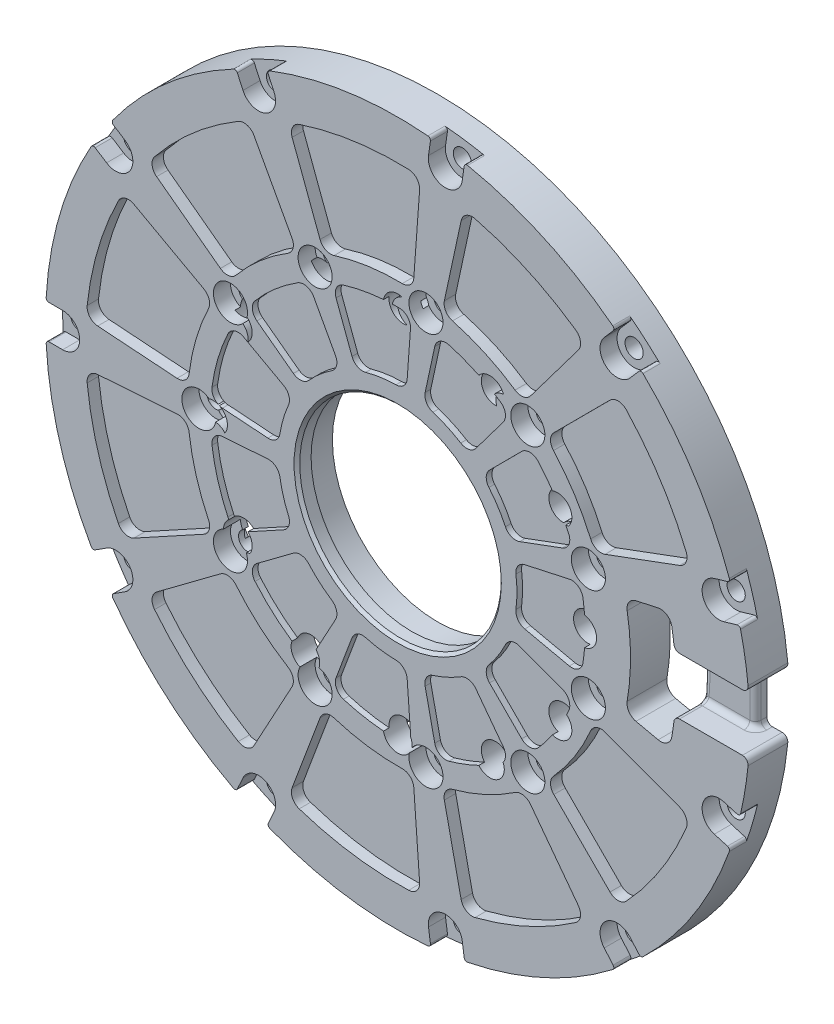
SolidWorks part; units mm, degrees
material "ABS"
ref_plane "Front Plane" through (0, 0, 0) normal (0, 0, 1) x (1, 0, 0)
ref_plane "Top Plane" through (0, 0, 0) normal (0, 1, 0) x (1, 0, 0)
ref_plane "Right Plane" through (0, 0, 0) normal (1, 0, 0) x (0, 0, -1)
ref_plane "Plane1" through (0, 0, 15) normal (0, 0, 1) x (1, 0, 0)
sketch "Sketch1" plane through (0, 0, 15) normal (0, 0, 1) x (1, 0, 0)
  circle A0 centre (0, 0) radius 39.1
  circle A1 centre (0, 0) radius 32.5 construction
  circle A2 centre (32.5, 0) radius 2.525
  circle A3 centre (28.1458, -16.25) radius 2.525
  circle A4 centre (16.25, -28.1458) radius 2.525
  circle A5 centre (0, -32.5) radius 2.525
  circle A6 centre (-16.25, -28.1458) radius 2.525
  circle A7 centre (-28.1458, -16.25) radius 2.525
  circle A8 centre (-32.5, 0) radius 2.525
  circle A9 centre (-28.1458, 16.25) radius 2.525
  circle A10 centre (-16.25, 28.1458) radius 2.525
  circle A11 centre (0, 32.5) radius 2.525
  circle A12 centre (16.25, 28.1458) radius 2.525
  circle A13 centre (0, 0) radius 16
  circle A14 centre (28.1458, 16.25) radius 2.525
  point P28 (0, 0)
extrude "Boss-Extrude1" add sketch "Sketch1" along normal blind 7
sketch "Sketch2" plane through (0, 0, 15) normal (0, 0, -1) x (-1, 0, 0)
  circle A0 centre (0, 0) radius 18.5
  dimension "D1" = 37
extrude "Cut-Extrude1" cut sketch "Sketch2" against normal blind 4.5
sketch "Sketch3" plane through (0, 0, 22) normal (0, 0, 1) x (1, 0, 0)
  circle A1 centre (-16.25, 28.1458) radius 2.55
  circle A2 centre (1.5464, 32.4632) radius 2.55
  circle A4 centre (18.8518, 26.4737) radius 2.55
  circle A6 centre (30.172, 12.079) radius 2.55
  circle A8 centre (31.9127, -6.1507) radius 2.55
  circle A10 centre (23.5214, -22.4276) radius 2.55
  circle A12 centre (7.6622, -31.5839) radius 2.55
  circle A14 centre (-10.6297, -30.7125) radius 2.55
  circle A16 centre (-25.5467, -20.0902) radius 2.55
  circle A18 centre (-32.3528, -3.0893) radius 2.55
  circle A20 centre (-28.8872, 14.8924) radius 2.55
  point P36 (0, 0)
  dimension "D1" = 5.1
  dimension "D3" = 11
extrude "Boss-Extrude2" add sketch "Sketch3" against normal blind 2
chamfer "Chamfer3" distance 0.5 angle 45 11 edges at (35.025, 0, 15) (30.6708, -16.25, 15) (18.775, -28.1458, 15) (2.525, -32.5, 15) (-13.725, -28.1458, 15) (-25.6208, -16.25, 15) (-29.975, 0, 15) (-25.6208, 16.25, 15) (-13.725, 28.1458, 15) (2.525, 32.5, 15) (18.775, 28.1458, 15)
sketch "Sketch4" plane through (0, 0, 15) normal (0, 0, -1) x (-1, 0, 0)
  arc A0 (6.4473, 32.3131) -> (-6.4473, 32.3131) centre (0, 32.5) ccw
  circle A1 centre (0, 0) radius 39.1
  arc A2 (22.8936, 23.6978) -> (12.046, 30.6692) centre (17.5708, 27.3407) ccw
  arc A3 (32.0713, 7.5587) -> (26.7147, 19.288) centre (29.563, 13.501) ccw
  arc A4 (31.0666, -10.9803) -> (32.9017, 1.783) centre (32.1692, -4.6252) ccw
  arc A5 (20.1985, -26.0331) -> (28.6427, -16.288) centre (24.5619, -21.283) ccw
  arc A6 (2.9175, -32.8206) -> (15.2898, -29.1878) centre (9.1563, -31.1835) ccw
  arc A7 (-15.2898, -29.1878) -> (-2.9175, -32.8206) centre (-9.1563, -31.1835) ccw
  arc A8 (-28.6427, -16.288) -> (-20.1985, -26.0331) centre (-24.5619, -21.283) ccw
  arc A9 (-32.9017, 1.783) -> (-31.0666, -10.9803) centre (-32.1692, -4.6252) ccw
  arc A10 (-26.7147, 19.288) -> (-32.0713, 7.5587) centre (-29.563, 13.501) ccw
  arc A11 (-12.046, 30.6692) -> (-22.8936, 23.6978) centre (-17.5708, 27.3407) ccw
  arc A12 (-32.0713, 7.5587) -> (-32.9017, 1.783) centre (0, 0) ccw
  arc A13 (-22.8936, 23.6978) -> (-26.7147, 19.288) centre (0, 0) ccw
  arc A14 (-6.4473, 32.3131) -> (-12.046, 30.6692) centre (0, 0) ccw
  arc A15 (12.046, 30.6692) -> (6.4473, 32.3131) centre (0, 0) ccw
  arc A16 (26.7147, 19.288) -> (22.8936, 23.6978) centre (0, 0) ccw
  arc A17 (32.9017, 1.783) -> (32.0713, 7.5587) centre (0, 0) ccw
  arc A18 (28.6427, -16.288) -> (31.0666, -10.9803) centre (0, 0) ccw
  arc A19 (15.2898, -29.1878) -> (20.1985, -26.0331) centre (0, 0) ccw
  arc A20 (-2.9175, -32.8206) -> (2.9175, -32.8206) centre (0, 0) ccw
  arc A21 (-20.1985, -26.0331) -> (-15.2898, -29.1878) centre (0, 0) ccw
  arc A22 (-31.0666, -10.9803) -> (-28.6427, -16.288) centre (0, 0) ccw
  point P28 (0, 0)
  circle M36 centre (0, 0) radius 39.1
  dimension "D1" = 12.9
  dimension "D2" = 78.2
  dimension "D4" = 65.9
  dimension "D3" = 11
extrude "Cut-Extrude2" cut sketch "Sketch4" against normal blind 3 contours A15 A2 A0 M36 | A16 A3 A2 M36 | A17 A4 A3 M36 | A18 A5 A4 M36 | A19 A6 A5 M36 | A20 A7 A6 M36 | A21 A8 A7 M36 | A22 A9 A8 M36 | A12 A10 A9 M36 | A13 A11 A10 M36 | A14 A0 A11 M36 region at (37.9941, 0, 15)
fillet "Fillet1" radius 4 rebuild error yes
sketch "Sketch5" plane through (0, 0, 22) normal (0, 0, 1) x (1, 0, 0)
  circle A0 centre (0, 0) radius 17.75
  dimension "D1" = 35.5
extrude "Cut-Extrude3" cut sketch "Sketch5" against normal blind 10
chamfer "Chamfer5" distance 0.5 angle 45 1 edges at (17.75, 0, 22)
sketch "Sketch7" plane through (0, 0, 22) normal (0, 0, 1) x (1, 0, 0)
  line L0 (0, 0) -> (-35, 0) construction
  circle A0 centre (-35, 0) radius 1.575
  circle A1 centre (-29.4439, 18.9224) radius 1.575
  circle A2 centre (-14.5395, 31.8371) radius 1.575
  circle A3 centre (4.981, 34.6438) radius 1.575
  circle A4 centre (22.9201, 26.4512) radius 1.575
  circle A5 centre (33.5823, 9.8606) radius 1.575
  circle A6 centre (33.5823, -9.8606) radius 1.575
  circle A7 centre (22.9201, -26.4512) radius 1.575
  circle A8 centre (4.981, -34.6438) radius 1.575
  circle A9 centre (-14.5395, -31.8371) radius 1.575
  circle A10 centre (-29.4439, -18.9224) radius 1.575
  point P26 (0, 0)
  dimension "D2" = 3.15
  dimension "D1" = 35
  dimension "D3" = 11
extrude "Cut-Extrude5" cut sketch "Sketch7" against normal through all
sketch "Sketch8" plane through (0, 0, 22) normal (0, 0, 1) x (1, 0, 0)
  circle A0 centre (0, 0) radius 39.1
  circle A1 centre (0, 0) radius 62
  dimension "D1" = 124
extrude "Boss-Extrude3" add sketch "Sketch8" against normal blind 7
sketch "Sketch9" plane through (0, 0, 15) normal (0, 0, -1) x (-1, 0, 0)
  circle A0 centre (0, 0) radius 39.1
  circle A1 centre (0, 0) radius 40
  dimension "D1" = 80
  dimension "D2" = 78.2
extrude "Cut-Extrude6" cut sketch "Sketch9" against normal blind 3
sketch "Sketch11" plane through (0, 0, 22) normal (0, 0, 1) x (1, 0, 0)
  line L0 (0, 0) -> (-59, 0) construction
  circle A0 centre (-59, 0) radius 1.6
  circle A1 centre (-49.634, 31.8978) radius 1.6
  circle A2 centre (-24.5095, 53.6683) radius 1.6
  circle A3 centre (8.3966, 58.3995) radius 1.6
  circle A4 centre (38.6368, 44.5892) radius 1.6
  circle A5 centre (56.6101, 16.6222) radius 1.6
  circle A6 centre (56.6101, -16.6222) radius 1.6
  circle A7 centre (38.6368, -44.5892) radius 1.6
  circle A8 centre (8.3966, -58.3995) radius 1.6
  circle A9 centre (-24.5095, -53.6683) radius 1.6
  circle A10 centre (-49.634, -31.8978) radius 1.6
  point P27 (0, 0)
  dimension "D2" = 3.2
  dimension "D1" = 59
  dimension "D3" = 11
extrude "Cut-Extrude7" cut sketch "Sketch11" against normal through all
sketch "Sketch12" plane through (0, 0, 22) normal (0, 0, 1) x (1, 0, 0)
  line L0 (0, 0) -> (-59, 0) construction
  line L1 (0, 0) -> (-49.634, -31.8978) construction
  line L2 (-52.8332, -3.6945) -> (-38.8538, -2.7169)
  line L3 (-46.4435, -25.4558) -> (-34.1548, -18.7203)
  line L4 (-30.8601, -2.1579) -> (-22.8571, -1.5983)
  line L5 (-27.1278, -14.8688) -> (-20.0927, -11.0129)
  line L6 (-27.1278, 14.8688) -> (-20.0927, 11.0129)
  line L7 (-30.8601, 2.1579) -> (-22.8571, 1.5983)
  line L8 (-14.7827, 27.1749) -> (-10.9491, 20.1275)
  line L9 (-24.7945, 18.4996) -> (-18.3645, 13.7021)
  line L10 (2.2559, 30.8531) -> (1.6708, 22.8519)
  line L11 (-10.8568, 28.9677) -> (-8.0413, 21.4555)
  line L12 (18.5782, 24.7356) -> (13.7603, 18.3209)
  line L13 (6.5278, 30.2388) -> (4.835, 22.3969)
  line L14 (29.002, 10.7648) -> (21.4809, 7.9732)
  line L15 (21.8399, 21.9093) -> (16.1761, 16.2275)
  line L16 (30.218, -6.6237) -> (22.3815, -4.906)
  line L17 (30.218, 6.6237) -> (22.3815, 4.906)
  line L18 (21.8399, -21.9093) -> (16.1761, -16.2275)
  line L19 (29.002, -10.7648) -> (21.4809, -7.9732)
  line L20 (6.5278, -30.2388) -> (4.835, -22.3969)
  line L21 (18.5782, -24.7356) -> (13.7603, -18.3209)
  line L22 (-10.8568, -28.9677) -> (-8.0413, -21.4555)
  line L23 (2.2559, -30.8531) -> (1.6708, -22.8519)
  line L24 (-24.7945, -18.4996) -> (-18.3645, -13.7021)
  line L25 (-14.7827, -27.1749) -> (-10.9491, -20.1275)
  line L26 (-46.4435, 25.4558) -> (-34.1548, 18.7203)
  line L27 (-52.8332, 3.6945) -> (-38.8538, 2.7169)
  line L28 (-25.3083, 46.5241) -> (-18.6119, 34.214)
  line L29 (-42.4488, 31.6718) -> (-31.217, 23.2916)
  line L30 (3.8621, 52.8212) -> (2.8402, 38.845)
  line L31 (-18.5871, 49.5935) -> (-13.6691, 36.4713)
  line L32 (31.8063, 42.3481) -> (23.3905, 31.143)
  line L33 (11.1758, 51.7697) -> (8.2187, 38.0717)
  line L34 (49.6523, 18.4297) -> (36.5145, 13.5533)
  line L35 (37.3905, 37.5093) -> (27.4971, 27.5845)
  line L36 (51.734, -11.34) -> (38.0454, -8.3395) [skipped]
  line L37 (51.734, 11.34) -> (38.0454, 8.3395) [skipped]
  line L38 (37.3905, -37.5093) -> (27.4971, -27.5845)
  line L39 (49.6523, -18.4297) -> (36.5145, -13.5533)
  line L40 (11.1758, -51.7697) -> (8.2187, -38.0717)
  line L41 (31.8063, -42.3481) -> (23.3905, -31.143)
  line L42 (-18.5871, -49.5935) -> (-13.6691, -36.4713)
  line L43 (3.8621, -52.8212) -> (2.8402, -38.845)
  line L44 (-42.4488, -31.6718) -> (-31.217, -23.2916)
  line L45 (-25.3083, -46.5241) -> (-18.6119, -34.214)
  arc A0 (-54.6822, -5.9043) -> (-49.1937, -24.5964) centre (0, 0) ccw
  arc A1 (-36.7289, -4.4704) -> (-33.3152, -16.0964) centre (0, 0) ccw
  arc A2 (-46.4435, -25.4558) -> (-49.1937, -24.5964) centre (-47.4048, -23.702) cw
  arc A3 (-34.1548, -18.7203) -> (-33.3152, -16.0964) centre (-35.1161, -16.9665) ccw
  arc A4 (-38.8538, -2.7169) -> (-36.7289, -4.4704) centre (-38.7143, -4.7121) cw
  arc A5 (-52.8332, -3.6945) -> (-54.6822, -5.9043) centre (-52.6937, -5.6896) ccw
  arc A6 (-32.7025, -4.421) -> (-29.9013, -13.9611) centre (0, 0) ccw
  arc A7 (-20.7421, -3.281) -> (-19.2232, -8.4539) centre (0, 0) ccw
  arc A8 (-27.1278, -14.8688) -> (-29.9013, -13.9611) centre (-28.0891, -13.115) cw
  arc A9 (-20.0927, -11.0129) -> (-19.2232, -8.4539) centre (-21.054, -9.259) ccw
  arc A10 (-22.8571, -1.5983) -> (-20.7421, -3.281) centre (-22.7176, -3.5934) cw
  arc A11 (-30.8601, -2.1579) -> (-32.7025, -4.421) centre (-30.7205, -4.1531) ccw
  arc A12 (-29.9013, 13.9611) -> (-32.7025, 4.421) centre (0, 0) ccw
  arc A13 (-27.1278, 14.8688) -> (-29.9013, 13.9611) centre (-28.0891, 13.115) ccw
  arc A14 (-20.0927, 11.0129) -> (-19.2232, 8.4539) centre (-21.054, 9.259) cw
  arc A15 (-19.2232, 8.4539) -> (-20.7421, 3.281) centre (0, 0) ccw
  arc A16 (-22.8571, 1.5983) -> (-20.7421, 3.281) centre (-22.7176, 3.5934) ccw
  arc A17 (-30.8601, 2.1579) -> (-32.7025, 4.421) centre (-30.7205, 4.1531) cw
  arc A18 (-17.6066, 27.9107) -> (-25.1209, 21.3995) centre (0, 0) ccw
  arc A19 (-14.7827, 27.1749) -> (-17.6066, 27.9107) centre (-16.5395, 26.2191) ccw
  arc A20 (-10.9491, 20.1275) -> (-11.6011, 17.5047) centre (-12.7059, 19.1718) cw
  arc A21 (-11.6011, 17.5047) -> (-15.6755, 13.9742) centre (0, 0) ccw
  arc A22 (-18.3645, 13.7021) -> (-15.6755, 13.9742) centre (-17.1685, 15.305) ccw
  arc A23 (-24.7945, 18.4996) -> (-25.1209, 21.3995) centre (-23.5984, 20.1026) cw
  arc A24 (0.278, 32.9988) -> (-9.5636, 31.5838) centre (0, 0) ccw
  arc A25 (2.2559, 30.8531) -> (0.278, 32.9988) centre (0.2612, 30.9989) ccw
  arc A26 (1.6708, 22.8519) -> (-0.2957, 20.9979) centre (-0.3238, 22.9977) cw
  arc A27 (-0.2957, 20.9979) -> (-5.6321, 20.2307) centre (0, 0) ccw
  arc A28 (-8.0413, 21.4555) -> (-5.6321, 20.2307) centre (-6.1685, 22.1574) ccw
  arc A29 (-10.8568, 28.9677) -> (-9.5636, 31.5838) centre (-8.984, 29.6696) cw
  arc A30 (18.0744, 27.6101) -> (9.0301, 31.7405) centre (0, 0) ccw
  arc A31 (18.5782, 24.7356) -> (18.0744, 27.6101) centre (16.979, 25.9367) ccw
  arc A32 (13.7603, 18.3209) -> (11.1036, 17.8244) centre (12.1611, 19.522) cw
  arc A33 (11.1036, 17.8244) -> (6.1995, 20.0641) centre (0, 0) ccw
  arc A34 (4.835, 22.3969) -> (6.1995, 20.0641) centre (6.7899, 21.9749) ccw
  arc A35 (6.5278, 30.2388) -> (9.0301, 31.7405) centre (8.4828, 29.8168) cw
  arc A36 (30.1323, 13.4553) -> (24.7568, 21.8198) centre (0, 0) ccw
  arc A37 (29.002, 10.7648) -> (30.1323, 13.4553) centre (28.3061, 12.6398) ccw
  arc A38 (21.4809, 7.9732) -> (18.9776, 8.9918) centre (20.7849, 9.8482) cw
  arc A39 (18.9776, 8.9918) -> (16.0628, 13.5273) centre (0, 0) ccw
  arc A40 (16.1761, 16.2275) -> (16.0628, 13.5273) centre (17.5926, 14.8156) ccw
  arc A41 (21.8399, 21.9093) -> (24.7568, 21.8198) centre (23.2564, 20.4974) cw
  arc A42 (32.6234, -4.9714) -> (32.6234, 4.9714) centre (0, 0) ccw
  arc A43 (30.218, -6.6237) -> (32.6234, -4.9714) centre (30.6462, -4.6701) ccw
  arc A44 (22.3815, -4.906) -> (20.8263, -2.6957) centre (22.8097, -2.9524) cw
  arc A45 (20.8263, -2.6957) -> (20.8263, 2.6957) centre (0, 0) ccw
  arc A46 (22.3815, 4.906) -> (20.8263, 2.6957) centre (22.8097, 2.9524) ccw
  arc A47 (30.218, 6.6237) -> (32.6234, 4.9714) centre (30.6462, 4.6701) cw
  arc A48 (24.7568, -21.8198) -> (30.1323, -13.4553) centre (0, 0) ccw
  arc A49 (21.8399, -21.9093) -> (24.7568, -21.8198) centre (23.2564, -20.4974) ccw
  arc A50 (16.1761, -16.2275) -> (16.0628, -13.5273) centre (17.5926, -14.8156) cw
  arc A51 (16.0628, -13.5273) -> (18.9776, -8.9918) centre (0, 0) ccw
  arc A52 (21.4809, -7.9732) -> (18.9776, -8.9918) centre (20.7849, -9.8482) ccw
  arc A53 (29.002, -10.7648) -> (30.1323, -13.4553) centre (28.3061, -12.6398) cw
  arc A54 (9.0301, -31.7405) -> (18.0744, -27.6101) centre (0, 0) ccw
  arc A55 (6.5278, -30.2388) -> (9.0301, -31.7405) centre (8.4828, -29.8168) ccw
  arc A56 (4.835, -22.3969) -> (6.1995, -20.0641) centre (6.7899, -21.9749) cw
  arc A57 (6.1995, -20.0641) -> (11.1036, -17.8244) centre (0, 0) ccw
  arc A58 (13.7603, -18.3209) -> (11.1036, -17.8244) centre (12.1611, -19.522) ccw
  arc A59 (18.5782, -24.7356) -> (18.0744, -27.6101) centre (16.979, -25.9367) cw
  arc A60 (-9.5636, -31.5838) -> (0.278, -32.9988) centre (0, 0) ccw
  arc A61 (-10.8568, -28.9677) -> (-9.5636, -31.5838) centre (-8.984, -29.6696) ccw
  arc A62 (-8.0413, -21.4555) -> (-5.6321, -20.2307) centre (-6.1685, -22.1574) cw
  arc A63 (-5.6321, -20.2307) -> (-0.2957, -20.9979) centre (0, 0) ccw
  arc A64 (1.6708, -22.8519) -> (-0.2957, -20.9979) centre (-0.3238, -22.9977) ccw
  arc A65 (2.2559, -30.8531) -> (0.278, -32.9988) centre (0.2612, -30.9989) cw
  arc A66 (-25.1209, -21.3995) -> (-17.6066, -27.9107) centre (0, 0) ccw
  arc A67 (-24.7945, -18.4996) -> (-25.1209, -21.3995) centre (-23.5984, -20.1026) ccw
  arc A68 (-18.3645, -13.7021) -> (-15.6755, -13.9742) centre (-17.1685, -15.305) cw
  arc A69 (-15.6755, -13.9742) -> (-11.6011, -17.5047) centre (0, 0) ccw
  arc A70 (-10.9491, -20.1275) -> (-11.6011, -17.5047) centre (-12.7059, -19.1718) ccw
  arc A71 (-14.7827, -27.1749) -> (-17.6066, -27.9107) centre (-16.5395, -26.2191) cw
  arc A72 (-46.4435, 25.4558) -> (-49.1937, 24.5964) centre (-47.4048, 23.702) ccw
  arc A73 (-34.1548, 18.7203) -> (-33.3152, 16.0964) centre (-35.1161, 16.9665) cw
  arc A74 (-38.8538, 2.7169) -> (-36.7289, 4.4704) centre (-38.7143, 4.7121) ccw
  arc A75 (-52.8332, 3.6945) -> (-54.6822, 5.9043) centre (-52.6937, 5.6896) cw
  arc A76 (-49.1937, 24.5964) -> (-54.6822, 5.9043) centre (0, 0) ccw
  arc A77 (-33.3152, 16.0964) -> (-36.7289, 4.4704) centre (0, 0) ccw
  arc A78 (-25.3083, 46.5241) -> (-28.0865, 47.2879) centre (-27.0652, 45.5684) ccw
  arc A79 (-18.6119, 34.214) -> (-19.3242, 31.5527) centre (-20.3687, 33.2583) cw
  arc A80 (-31.217, 23.2916) -> (-28.4815, 23.6179) centre (-30.021, 24.8946) ccw
  arc A81 (-42.4488, 31.6718) -> (-42.8095, 34.5304) centre (-41.2528, 33.2748) cw
  arc A82 (-28.0865, 47.2879) -> (-42.8095, 34.5304) centre (0, 0) ccw
  arc A83 (-19.3242, 31.5527) -> (-28.4815, 23.6179) centre (0, 0) ccw
  arc A84 (3.8621, 52.8212) -> (1.9379, 54.9658) centre (1.8674, 52.9671) ccw
  arc A85 (2.8402, 38.845) -> (0.8022, 36.9913) centre (0.8455, 38.9908) cw
  arc A86 (-13.6691, 36.4713) -> (-11.1913, 35.2669) centre (-11.7963, 37.1732) ccw
  arc A87 (-18.5871, 49.5935) -> (-17.3451, 52.1934) centre (-16.7143, 50.2954) cw
  arc A88 (1.9379, 54.9658) -> (-17.3451, 52.1934) centre (0, 0) ccw
  arc A89 (0.8022, 36.9913) -> (-11.1913, 35.2669) centre (0, 0) ccw
  arc A90 (31.8063, 42.3481) -> (31.347, 45.1925) centre (30.2071, 43.5491) ccw
  arc A91 (23.3905, 31.143) -> (20.6738, 30.6854) centre (21.7913, 32.344) cw
  arc A92 (8.2187, 38.0717) -> (9.652, 35.7189) centre (10.1737, 37.6496) ccw
  arc A93 (11.1758, 51.7697) -> (13.6263, 53.2853) centre (13.1308, 51.3477) cw
  arc A94 (31.347, 45.1925) -> (13.6263, 53.2853) centre (0, 0) ccw
  arc A95 (20.6738, 30.6854) -> (9.652, 35.7189) centre (0, 0) ccw
  arc A96 (49.6523, 18.4297) -> (50.8037, 21.0709) centre (48.9563, 20.3047) ccw
  arc A97 (36.5145, 13.5533) -> (33.9817, 14.6371) centre (35.8186, 15.4283) cw
  arc A98 (27.4971, 27.5845) -> (27.4309, 24.8304) centre (28.9136, 26.1726) ccw
  arc A99 (37.3905, 37.5093) -> (40.2714, 37.4595) centre (38.807, 36.0974) cw
  arc A100 (50.8037, 21.0709) -> (40.2714, 37.4595) centre (0, 0) ccw
  arc A101 (33.9817, 14.6371) -> (27.4309, 24.8304) centre (0, 0) ccw
  arc A102 (51.734, -11.34) -> (54.1306, -9.7406) centre (52.1622, -9.3864) ccw [skipped]
  arc A103 (38.0454, -8.3395) -> (36.5006, -6.0584) centre (38.4736, -6.3859) cw [skipped]
  arc A104 (38.0454, 8.3395) -> (36.5006, 6.0584) centre (38.4736, 6.3859) ccw [skipped]
  arc A105 (51.734, 11.34) -> (54.1306, 9.7406) centre (52.1622, 9.3864) cw [skipped]
  arc A106 (54.1306, -9.7406) -> (54.1306, 9.7406) centre (0, 0) ccw [skipped]
  arc A107 (36.5006, -6.0584) -> (36.5006, 6.0584) centre (0, 0) ccw [skipped]
  arc A108 (37.3905, -37.5093) -> (40.2714, -37.4595) centre (38.807, -36.0974) ccw
  arc A109 (27.4971, -27.5845) -> (27.4309, -24.8304) centre (28.9136, -26.1726) cw
  arc A110 (36.5145, -13.5533) -> (33.9817, -14.6371) centre (35.8186, -15.4283) ccw
  arc A111 (49.6523, -18.4297) -> (50.8037, -21.0709) centre (48.9563, -20.3047) cw
  arc A112 (40.2714, -37.4595) -> (50.8037, -21.0709) centre (0, 0) ccw
  arc A113 (27.4309, -24.8304) -> (33.9817, -14.6371) centre (0, 0) ccw
  arc A114 (11.1758, -51.7697) -> (13.6263, -53.2853) centre (13.1308, -51.3477) ccw
  arc A115 (8.2187, -38.0717) -> (9.652, -35.7189) centre (10.1737, -37.6496) cw
  arc A116 (23.3905, -31.143) -> (20.6738, -30.6854) centre (21.7913, -32.344) ccw
  arc A117 (31.8063, -42.3481) -> (31.347, -45.1925) centre (30.2071, -43.5491) cw
  arc A118 (13.6263, -53.2853) -> (31.347, -45.1925) centre (0, 0) ccw
  arc A119 (9.652, -35.7189) -> (20.6738, -30.6854) centre (0, 0) ccw
  arc A120 (-18.5871, -49.5935) -> (-17.3451, -52.1934) centre (-16.7143, -50.2954) ccw
  arc A121 (-13.6691, -36.4713) -> (-11.1913, -35.2669) centre (-11.7963, -37.1732) cw
  arc A122 (2.8402, -38.845) -> (0.8022, -36.9913) centre (0.8455, -38.9908) ccw
  arc A123 (3.8621, -52.8212) -> (1.9379, -54.9658) centre (1.8674, -52.9671) cw
  arc A124 (-17.3451, -52.1934) -> (1.9379, -54.9658) centre (0, 0) ccw
  arc A125 (-11.1913, -35.2669) -> (0.8022, -36.9913) centre (0, 0) ccw
  arc A126 (-42.4488, -31.6718) -> (-42.8095, -34.5304) centre (-41.2528, -33.2748) ccw
  arc A127 (-31.217, -23.2916) -> (-28.4815, -23.6179) centre (-30.021, -24.8946) cw
  arc A128 (-18.6119, -34.214) -> (-19.3242, -31.5527) centre (-20.3687, -33.2583) ccw
  arc A129 (-25.3083, -46.5241) -> (-28.0865, -47.2879) centre (-27.0652, -45.5684) cw
  arc A130 (-42.8095, -34.5304) -> (-28.0865, -47.2879) centre (0, 0) ccw
  arc A131 (-28.4815, -23.6179) -> (-19.3242, -31.5527) centre (0, 0) ccw
  point P152 (0, 0)
  point P274 (0, 0)
  dimension "D1" = 55
  dimension "D2" = 37
  dimension "D5" = 2
  dimension "D6" = 33
  dimension "D7" = 21
  dimension "D8" = 4
  dimension "D10" = 2
  dimension "D3" = 4
  dimension "D4" = 4
  dimension "D9" = 4
  dimension "D11" = 11
  dimension "D12" = 11
extrude "Cut-Extrude9" cut sketch "Sketch12" against normal blind 1 contours A47 L17 A46 A45 A44 L16 A43 A42 | A53 L19 A52 A51 A50 L18 A49 A48 | A59 L21 A58 A57 A56 L20 A55 A54 | A65 L23 A64 A63 A62 L22 A61 A60 | L4 A11 A6 A8 L5 A9 A7 A10 | A71 L25 A70 A69 A68 L24 A67 A66 | A17 L7 A16 A15 A14 L6 A13 A12 | A23 L9 A22 A21 A20 L8 A19 A18 | A29 L11 A28 A27 A26 L10 A25 A24 | A35 L13 A34 A33 A32 L12 A31 A30 | A41 L15 A40 A39 A38 L14 A37 A36 region at (-26.1323, -7.6731, 22) region at (-26.1323, 7.6731, 22) region at (-17.8355, 20.5832, 22) region at (-3.876, 26.9583, 22) region at (11.3141, 24.7743, 22) region at (22.912, 14.7246, 22) region at (27.2355, 0, 22) region at (22.912, -14.7246, 22) region at (11.3141, -24.7743, 22) region at (-3.876, -26.9583, 22) region at (-17.8355, -20.5832, 22)
extrude "Cut-Extrude10" cut sketch "Sketch12<3>" against normal blind 2 contours A113 A109 L38 A108 A112 A111 L39 A110 | A119 A115 L40 A114 A118 A117 L41 A116 | A125 A121 L42 A120 A124 A123 L43 A122 | A131 A127 L44 A126 A130 A129 L45 A128 | L2 A5 A0 A2 L3 A3 A1 A4 | A77 A73 L26 A72 A76 A75 L27 A74 | A83 A79 L28 A78 A82 A81 L29 A80 | A89 A85 L30 A84 A88 A87 L31 A86 | A95 A91 L32 A90 A94 A93 L33 A92 | A101 A97 L34 A96 A100 A99 L35 A98 region at (-44.3596, -13.0252, 22) region at (-44.3596, 13.0252, 22) region at (-30.2757, 34.9401, 22) region at (-6.5795, 45.7617, 22) region at (19.2056, 42.0544, 22) region at (38.8931, 24.9951, 22) region at (38.8931, -24.9951, 22) region at (19.2056, -42.0544, 22) region at (-6.5795, -45.7617, 22) region at (-30.2757, -34.9401, 22)
sketch "Sketch12<3>" plane through (0, 0, 22) normal (0, 0, 1) x (1, 0, 0) same geometry as "Sketch12"
sketch "Sketch13" plane through (0, 0, 22) normal (0, 0, 1) x (1, 0, 0)
  line L0 (0, 0) -> (56.6101, 16.6222) construction
  line L1 (0, 0) -> (56.6101, -16.6222) construction
  line L2 (45.8684, 10.0543) -> (41.9573, 9.197)
  line L3 (45.8684, -10.0543) -> (41.9573, -9.197)
  arc A0 (48.2667, 8.4454) -> (48.2667, -8.4454) centre (0, 0) cw
  arc A1 (40.4141, 6.9065) -> (40.4141, -6.9065) centre (0, 0) cw
  arc A2 (41.9573, -9.197) -> (40.4141, -6.9065) centre (42.3855, -7.2434) cw
  arc A3 (45.8684, -10.0543) -> (48.2667, -8.4454) centre (46.2966, -8.1007) ccw
  arc A4 (45.8684, 10.0543) -> (48.2667, 8.4454) centre (46.2966, 8.1007) cw
  arc A5 (41.9573, 9.197) -> (40.4141, 6.9065) centre (42.3855, 7.2434) ccw
  dimension "D1" = 41
  dimension "D2" = 49
  dimension "D5" = 2
  dimension "D3" = 4
  dimension "D4" = 4
extrude "Cut-Extrude11" cut sketch "Sketch13" against normal through all
sketch "Sketch15" plane through (0, 0, 22) normal (0, 0, 1) x (1, 0, 0)
  line L0 (49, 0) -> (62, 0)
  line L1 (49, 5) -> (48.2052, 5)
  line L2 (49, 0) -> (62, 0)
  line L3 (49, 0) -> (49, -5)
  line L4 (49, -5) -> (62, -5)
  line L5 (62, 0) -> (62, -5)
  line L6 (49, 0) -> (62, 0)
  line L7 (49, 0) -> (49, 5)
  line L8 (49, 5) -> (62, 5)
  line L9 (62, 0) -> (62, 5)
  line L10 (49, -5) -> (48.2052, -5)
  line L11 (48.2052, 5) -> (48.2052, -5)
  arc A0 (48.2667, -8.4454) -> (48.2667, 8.4454) centre (0, 0) ccw construction
  circle A1 centre (0, 0) radius 62 construction
  dimension "D1" = 5
  dimension "D2" = 5
extrude "Cut-Extrude14" cut sketch "Sketch15" against normal blind 5 contours L0 L9 L8 L7 | L5 L0 L3 L4 | L1 L11 L10 L3 L7 region at (55.5, 2.5, 22) region at (55.5, -2.5, 22) region at (48.6026, 0, 22)
sketch "Sketch16" plane through (0, 0, 22) normal (0, 0, 1) x (1, 0, 0)
  line L0 (49, 5) -> (62, 5) construction
  line L1 (62, -5) -> (58, -5)
  line L2 (62, -5) -> (62, 5)
  line L3 (62, 5) -> (58, 5)
  line L4 (58, -5) -> (58, 5)
  dimension "D1" = 4
extrude "Cut-Extrude15" cut sketch "Sketch16" against normal through all
fillet "Fillet3" radius 1 10 edges at (58, -5, 16) (48.7442, -5, 19.5) (48.7442, 5, 19.5) (58, 5, 16) (53.3721, -5, 17) (49, 0, 17) (53.3721, 5, 17) (58, 0, 17) (61.7981, -5, 18.5) (61.7981, 5, 18.5)
sketch "Sketch17" plane through (0, 0, 22) normal (0, 0, 1) x (1, 0, 0)
  line L0 (-59, 3) -> (-61.8451, 3)
  line L1 (-59, -3) -> (-61.8451, -3)
  line L2 (-50.4055, 35.9598) -> (-51.3701, 36.5797)
  line L3 (-61.8451, 3) -> (-62.9918, 3)
  line L5 (-61.8451, -3) -> (-62.9918, -3)
  line L6 (-62.9918, 3) -> (-62.9918, -3)
  line L7 (-48.012, 34.4216) -> (-50.4055, 35.9598)
  line L8 (-51.2559, 29.374) -> (-53.6493, 30.9122)
  line L9 (-53.6493, 30.9122) -> (-54.614, 31.5322)
  line L10 (-51.3701, 36.5797) -> (-54.614, 31.5322)
  line L11 (-22.9625, 57.5025) -> (-23.4388, 58.5456)
  line L12 (-21.7806, 54.9145) -> (-22.9625, 57.5025)
  line L13 (-27.2384, 52.422) -> (-28.4203, 55.01)
  line L14 (-28.4203, 55.01) -> (-28.8966, 56.0531)
  line L15 (-23.4388, 58.5456) -> (-28.8966, 56.0531)
  line L16 (11.7709, 60.7887) -> (11.9341, 61.9237)
  line L17 (11.366, 57.9725) -> (11.7709, 60.7887)
  line L18 (5.4271, 58.8264) -> (5.832, 61.6426)
  line L19 (5.832, 61.6426) -> (5.9952, 62.7776)
  line L20 (11.9341, 61.9237) -> (5.9952, 62.7776)
  line L21 (42.7672, 44.7748) -> (43.5181, 45.6414)
  line L22 (40.904, 42.6246) -> (42.7672, 44.7748)
  line L23 (36.3695, 46.5538) -> (38.2327, 48.704)
  line L24 (38.2327, 48.704) -> (38.9836, 49.5706)
  line L25 (43.5181, 45.6414) -> (38.9836, 49.5706)
  line L26 (60.1851, 14.5453) -> (61.2854, 14.8684)
  line L27 (57.4553, 13.7437) -> (60.1851, 14.5453)
  line L28 (55.7649, 19.5007) -> (58.4948, 20.3023)
  line L29 (58.4948, 20.3023) -> (59.595, 20.6253)
  line L30 (61.2854, 14.8684) -> (59.595, 20.6253)
  line L31 (58.4948, -20.3023) -> (59.595, -20.6253)
  line L32 (55.7649, -19.5007) -> (58.4948, -20.3023)
  line L33 (57.4553, -13.7437) -> (60.1851, -14.5453)
  line L34 (60.1851, -14.5453) -> (61.2854, -14.8684)
  line L35 (59.595, -20.6253) -> (61.2854, -14.8684)
  line L36 (38.2327, -48.704) -> (38.9836, -49.5706)
  line L37 (36.3695, -46.5538) -> (38.2327, -48.704)
  line L38 (40.904, -42.6246) -> (42.7672, -44.7748)
  line L39 (42.7672, -44.7748) -> (43.5181, -45.6414)
  line L40 (38.9836, -49.5706) -> (43.5181, -45.6414)
  line L41 (5.832, -61.6426) -> (5.9952, -62.7776)
  line L42 (5.4271, -58.8264) -> (5.832, -61.6426)
  line L43 (11.366, -57.9725) -> (11.7709, -60.7887)
  line L44 (11.7709, -60.7887) -> (11.9341, -61.9237)
  line L45 (5.9952, -62.7776) -> (11.9341, -61.9237)
  line L46 (-28.4203, -55.01) -> (-28.8966, -56.0531)
  line L47 (-27.2384, -52.422) -> (-28.4203, -55.01)
  line L48 (-21.7806, -54.9145) -> (-22.9625, -57.5025)
  line L49 (-22.9625, -57.5025) -> (-23.4388, -58.5456)
  line L50 (-28.8966, -56.0531) -> (-23.4388, -58.5456)
  line L51 (-53.6493, -30.9122) -> (-54.614, -31.5322)
  line L52 (-51.2559, -29.374) -> (-53.6493, -30.9122)
  line L53 (-48.012, -34.4216) -> (-50.4055, -35.9598)
  line L54 (-50.4055, -35.9598) -> (-51.3701, -36.5797)
  line L55 (-54.614, -31.5322) -> (-51.3701, -36.5797)
  arc A0 (-59, -3) -> (-59, 3) centre (-59, 0) ccw
  arc A1 (-51.2559, 29.374) -> (-48.012, 34.4216) centre (-49.634, 31.8978) ccw
  arc A2 (-27.2384, 52.422) -> (-21.7806, 54.9145) centre (-24.5095, 53.6683) ccw
  arc A3 (5.4271, 58.8264) -> (11.366, 57.9725) centre (8.3966, 58.3995) ccw
  arc A4 (36.3695, 46.5538) -> (40.904, 42.6246) centre (38.6368, 44.5892) ccw
  arc A5 (55.7649, 19.5007) -> (57.4553, 13.7437) centre (56.6101, 16.6222) ccw
  arc A6 (57.4553, -13.7437) -> (55.7649, -19.5007) centre (56.6101, -16.6222) ccw
  arc A7 (40.904, -42.6246) -> (36.3695, -46.5538) centre (38.6368, -44.5892) ccw
  arc A8 (11.366, -57.9725) -> (5.4271, -58.8264) centre (8.3966, -58.3995) ccw
  arc A9 (-21.7806, -54.9145) -> (-27.2384, -52.422) centre (-24.5095, -53.6683) ccw
  arc A10 (-48.012, -34.4216) -> (-51.2559, -29.374) centre (-49.634, -31.8978) ccw
  point P80 (0, 0)
  dimension "D1" = 11
extrude "Cut-Extrude16" cut sketch "Sketch17" against normal blind 3
fillet "Fillet4" radius 0.5 22 edges at (-53.7185, 30.9567, 20.5) (-50.4747, 36.0042, 20.5) (-28.4545, 55.0849, 20.5) (-22.9967, 57.5774, 20.5) (11.7826, 60.8701, 20.5) (5.8437, 61.724, 20.5) (38.2866, 48.7662, 20.5) (42.8211, 44.837, 20.5) (60.2641, 14.5685, 20.5) (58.5737, 20.3254, 20.5) (58.5737, -20.3254, 20.5) (60.2641, -14.5685, 20.5) (38.2866, -48.7662, 20.5) (42.8211, -44.837, 20.5) (11.7826, -60.8701, 20.5) (5.8437, -61.724, 20.5) (-28.4545, -55.0849, 20.5) (-22.9967, -57.5774, 20.5) (-53.7185, -30.9567, 20.5) (-50.4747, -36.0042, 20.5) (-61.9274, -3, 20.5) (-61.9274, 3, 20.5)
sketch "Sketch18" plane through (0, 0, 22) normal (0, 0, 1) x (1, 0, 0)
  circle A0 centre (-35, 0) radius 3
  circle A1 centre (-29.4439, 18.9224) radius 3
  circle A2 centre (-14.5395, 31.8371) radius 3
  circle A3 centre (4.981, 34.6438) radius 3
  circle A4 centre (22.9201, 26.4512) radius 3
  circle A5 centre (33.5823, 9.8606) radius 3
  circle A6 centre (33.5823, -9.8606) radius 3
  circle A7 centre (22.9201, -26.4512) radius 3
  circle A8 centre (4.981, -34.6438) radius 3
  circle A9 centre (-14.5395, -31.8371) radius 3
  circle A10 centre (-29.4439, -18.9224) radius 3
  point P26 (0, 0)
  dimension "D1" = 6
  dimension "D2" = 11
extrude "Cut-Extrude17" cut sketch "Sketch18" against normal blind 3
fillet "Fillet5" radius 1 rebuild error yes
equation "\"RingPinShaft\"= 5.05"
equation "\"CenterBearingOut\"=32.00"
equation "\"OutputBearingOut\"=37.00"
equation "\"RingPostIn\"=5.15"
equation "\"CamBearingOut\"=15.1"
equation "\"DiskOutputShaft\"=10.1"
equation "\"CenterShaft\"=25.2"
equation "\"Eccentricity\"=2"
equation "\"CycCamShaft\"=10.05"
equation "\"m3Thru\"=3.15"
equation "\"m3Insert\"=4.2"
equation "\"D1@Sketch2\"=\"OutputBearingOut\""
equation "\"D2@Sketch7\"=\"m3Thru\""
equation "\"MountingHoleDiam\"=35"
equation "\"D1@Sketch7\"=\"MountingHoleDiam\""
